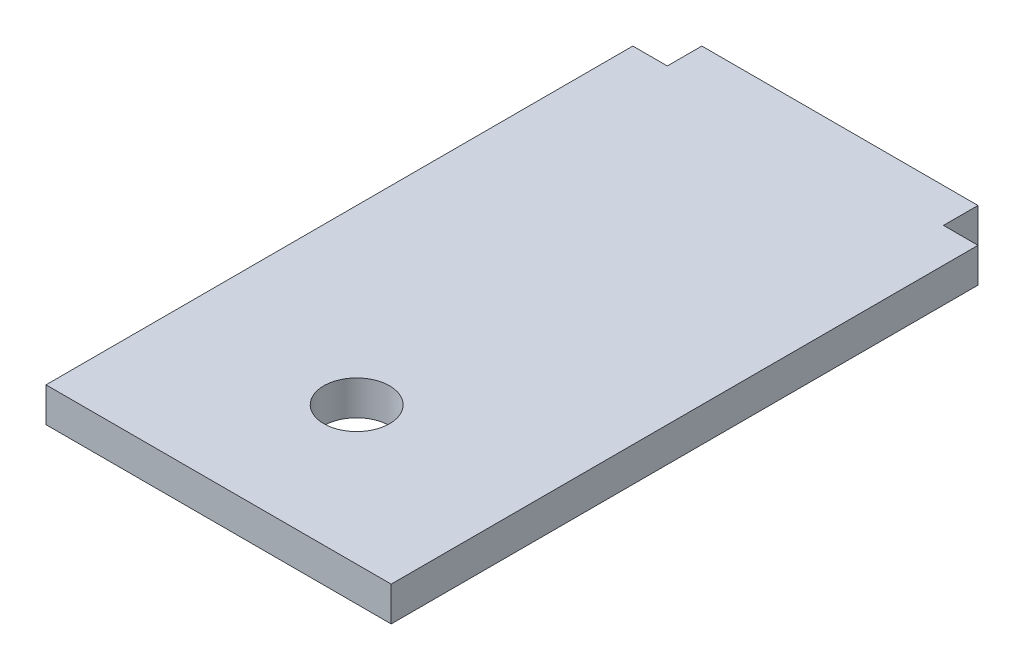
SolidWorks part; units mm, degrees
ref_plane "Front Plane" through (0, 0, 0) normal (0, 0, 1) x (1, 0, 0)
ref_plane "Top Plane" through (0, 0, 0) normal (0, 1, 0) x (1, 0, 0)
ref_plane "Right Plane" through (0, 0, 0) normal (1, 0, 0) x (0, 0, -1)
sketch "Sketch1" plane through (0, 0, 0) normal (0, 1, 0) x (1, 0, 0)
  line L0 (0, 85) -> (5, 85)
  line L1 (0, 0) -> (50, 0)
  line L2 (0, 0) -> (0, 85)
  line L3 (5, 90) -> (45, 90)
  line L4 (50, 0) -> (50, 85)
  line L5 (5, 90) -> (5, 85)
  line L6 (50, 85) -> (45, 85)
  line L7 (45, 85) -> (45, 90)
  line L8 (0, 20) -> (50, 20) construction
  circle A0 centre (25, 20) radius 4.7625
  point P10 (25, 0)
  dimension "D6" = 9.525
  dimension "D1" = 85
  dimension "D2" = 5
  dimension "D3" = 5
  dimension "D4" = 5
  dimension "D5" = 50
  dimension "D7" = 20
extrude "Hammer" add sketch "Sketch1" along normal blind 5
